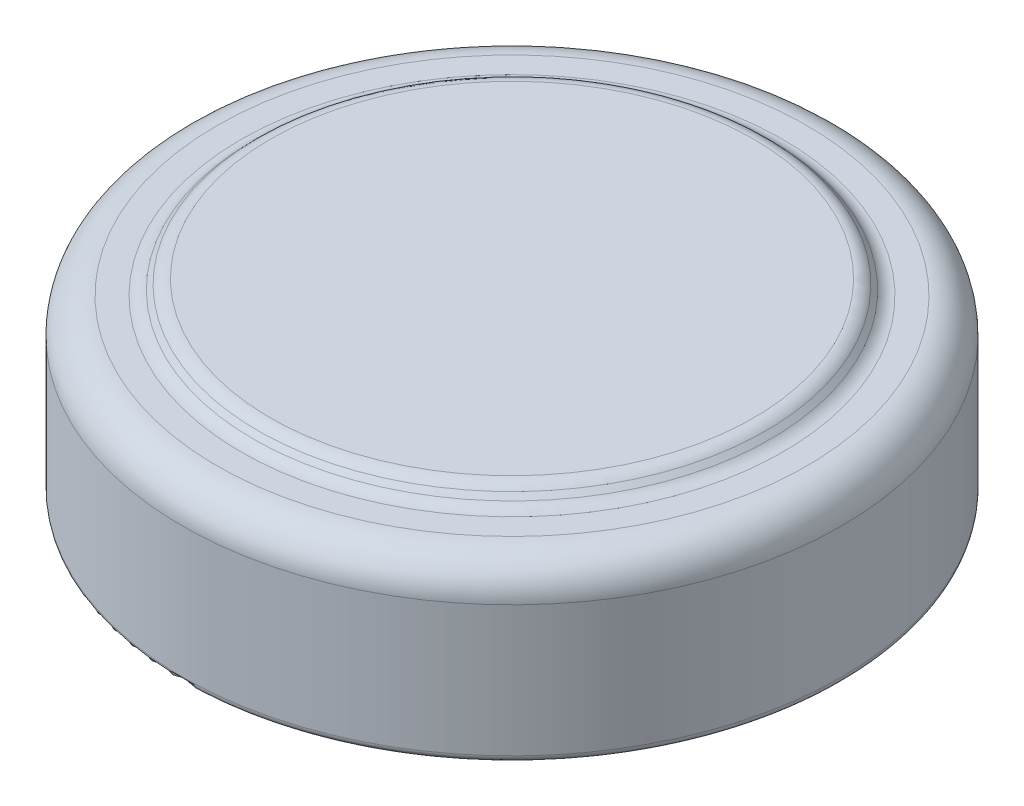
SolidWorks part; units mm, degrees
ref_plane "Front Plane" through (0, 0, 0) normal (0, 0, 1) x (1, 0, 0)
ref_plane "Top Plane" through (0, 0, 0) normal (0, 1, 0) x (1, 0, 0)
ref_plane "Right Plane" through (0, 0, 0) normal (1, 0, 0) x (0, 0, -1)
sketch "Sketch1" plane through (0, 0, 0) normal (0, 0, 1) x (1, 0, 0)
  line L0 (0, 0) -> (-4.65, 0)
  line L1 (-4.75, 0.1) -> (-4.75, 1.985)
  line L2 (-3.4814, 2.7) -> (0, 2.7)
  line L3 (0, 2.7) -> (0, 0)
  line L4 (-3.6582, 2.6268) -> (-3.7268, 2.5582)
  line L7 (-4.25, 2.485) -> (-3.9036, 2.485)
  arc A0 (-4.75, 1.985) -> (-4.25, 2.485) centre (-4.25, 1.985) cw
  arc A1 (-3.9036, 2.485) -> (-3.7268, 2.5582) centre (-3.9036, 2.735) ccw
  arc A2 (-3.4814, 2.7) -> (-3.6582, 2.6268) centre (-3.4814, 2.45) ccw
  arc A3 (-4.65, 0) -> (-4.75, 0.1) centre (-4.65, 0.1) cw
  point P9 (-4.75, 2.485)
  point P14 (-3.585, 2.7)
  point P17 (-4.75, 0)
  point P18 (-3.8, 2.485)
  dimension "D6" = 0.5
  dimension "D7" = 0.25
  dimension "D8" = 0.1
  dimension "D1" = 4.75
  dimension "D2" = 2.7
  dimension "D3" = 3.8
  dimension "D4" = 2.485
  dimension "D5" = 45
revolve "Revolve1" add sketch "Sketch1" angle 360 about L3
sketch "Sketch2" plane through (0, 0, 0) normal (0, -1, 0) x (1, 0, 0)
  line L0 (0.25, 0.25) -> (2, 0.25)
  line L1 (-0.25, 2) -> (0.25, 2)
  line L2 (-0.25, 2) -> (-0.25, 0.25)
  line L3 (-0.25, -2) -> (0.25, -2)
  line L4 (0.25, 2) -> (0.25, 0.25)
  line L5 (-2, 0.25) -> (-0.25, 0.25)
  line L6 (-2, 0.25) -> (-2, -0.25)
  line L7 (-2, -0.25) -> (-0.25, -0.25)
  line L8 (2, 0.25) -> (2, -0.25)
  line L9 (0.25, -0.25) -> (2, -0.25)
  line L10 (-0.25, -0.25) -> (-0.25, -2)
  line L11 (0.25, -0.25) -> (0.25, -2)
  circle A0 centre (0, 0) radius 3.25 construction
  text T0 "                           SR57" font "Century Gothic" height 1
  dimension "D1" = 6.5
  dimension "D2" = 0.5
  dimension "D3" = 0.5
  dimension "D4" = 0.25
  dimension "D5" = 0.25
  dimension "D6" = 4
  dimension "D7" = 2
  dimension "D8" = 2
  dimension "D9" = 4
wrap "Wrap1" sketch "Sketch2" wrap type scribe source sketch "Sketch2" face at (-4.65, 0, 0)
